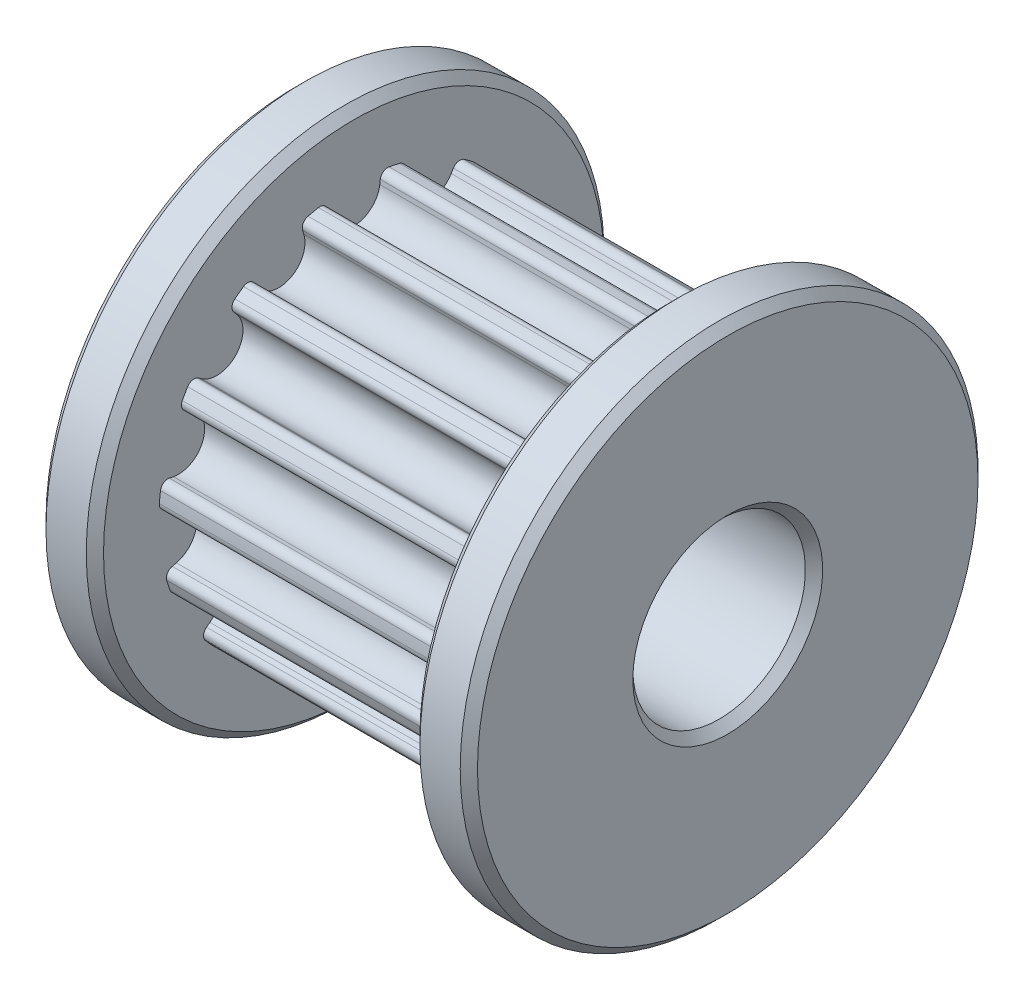
SolidWorks part; units mm, degrees
ref_plane "前视基准面" through (0, 0, 0) normal (0, 0, 1) x (1, 0, 0)
ref_plane "上视基准面" through (0, 0, 0) normal (0, 1, 0) x (1, 0, 0)
ref_plane "右视基准面" through (0, 0, 0) normal (1, 0, 0) x (0, 0, -1)
sketch "草图1" plane through (0, 0, 0) normal (0, 0, 1) x (1, 0, 0)
  line L0 (0, 0) -> (64.8368, 0) construction
  line L1 (0, 3) -> (0, 6.779)
  line L2 (0, 6.779) -> (11, 6.779)
  line L3 (11, 6.779) -> (11, 3)
  line L6 (11, 3) -> (0, 3)
  dimension "B" = 11
  dimension "d" = 6
  dimension "da" = 13.558
revolve "旋转1" add sketch "草图1" angle 360 about L0
sketch "草图6" plane through (0, 0, 0) normal (1, 0, 0) x (0, 0, -1)
  line L0 (0, 0) -> (0, 30.6512) construction
  line L1 (0.921, 6.4432) -> (0.9032, 6.2981)
  line L2 (1.4809, 6.6153) -> (1.6775, 8.2168)
  line L3 (-1.4809, 6.6153) -> (-1.6775, 8.2168)
  line L4 (-0.921, 6.4432) -> (-0.9032, 6.2981)
  circle A0 centre (0, 0) radius 6.779 construction
  circle A1 centre (0, 0) radius 5.499 construction
  arc A2 (-0.9032, 6.2981) -> (0.9032, 6.2981) centre (0, 6.409) ccw
  arc A3 (1.6775, 8.2168) -> (-1.6775, 8.2168) centre (0, 0) ccw
  arc A4 (0.921, 6.4432) -> (1.2261, 6.6672) centre (1.1791, 6.4115) cw
  arc A5 (1.2261, 6.6672) -> (1.4809, 6.6153) centre (0, 0) cw
  arc A6 (-1.2261, 6.6672) -> (-1.4809, 6.6153) centre (0, 0) ccw
  arc A7 (-0.921, 6.4432) -> (-1.2261, 6.6672) centre (-1.1791, 6.4115) ccw
  point P7 (0, 1.9)
  point P8 (0, 29.3712)
  point P15 (0.954, 6.7115)
  dimension "D1" = 10.998
  dimension "ra" = 0.26
  dimension "rf" = 0.91
  dimension "hg" = 1.28
  dimension "D3" = 0.26
  dimension "D4" = 1.6136
  dimension "angle" = 14
  dimension "bw" = 1.9
extrude "切除-拉伸2" cut sketch "草图6" along normal up to next
ref_axis "基准轴1" through (-1.4, 0, 0) along (1, 0, 0)
pattern_circular "阵列(圆周)3" count 15 over 360 about axis through (-1.4, 0, 0) along (1, 0, 0) of "切除-拉伸2"
sketch "草图7" plane through (0, 0, 0) normal (-1, 0, 0) x (0, 0, 1)
  circle A0 centre (0, 0) radius 9
  circle A1 centre (0, 0) radius 3 construction
  circle A2 centre (0, 0) radius 3
  dimension "D1" = 18
extrude "凸台-拉伸1" add sketch "草图7" along normal blind 2
extrude "凸台-拉伸2" add sketch "草图7<2>" against normal blind 2 from surface starting at face at (11, 0, 3)
sketch "草图7<2>" plane through (0, 0, 0) normal (-1, 0, 0) x (0, 0, 1) same geometry as "草图7"
chamfer "倒角1" distance 0.3 angle 45 6 edges at (0, 0, 9) (-2, 0, 9) (-2, 0, 3) (13, 0, 3) (13, 0, 9) (11, 0, 9)
equation "\"D1@草图6\" = \"da@草图1\"  - \"hg@草图6\" - \"hg@草图6\""
equation "\"D3@草图6\" = \"ra@草图6\""
